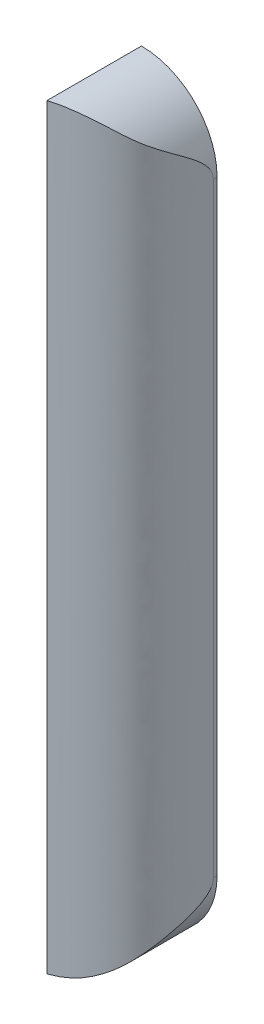
SolidWorks part; units mm, degrees
ref_plane "Front Plane" through (0, 0, 0) normal (0, 0, 1) x (1, 0, 0)
ref_plane "Top Plane" through (0, 0, 0) normal (0, 1, 0) x (1, 0, 0)
ref_plane "Right Plane" through (0, 0, 0) normal (1, 0, 0) x (0, 0, -1)
sketch "Sketch1" plane through (0, 0, 0) normal (0, 0, 1) x (1, 0, 0)
  line L1 (-4, 40) -> (4, 40)
  line L2 (-4, 40) -> (-4, -40)
  line L3 (-4, -40) -> (4, -40)
  line L4 (4, 40) -> (4, -40)
  point P4 (0, -40)
  point P6 (4, 0)
  dimension "D1" = 80
  dimension "D2" = 8
extrude "Extrude1" add sketch "Sketch1" along normal blind 0.4
sketch "Sketch2" plane through (0, -40, 0) normal (0, -1, 0) x (1, 0, 0)
  line L0 (-4, 0) -> (-4, 10)
  line L2 (4, 0.4) -> (4, 0)
  line L3 (4, 0) -> (-4, 0)
  spline S0 degree 3 poles (-4, 10) (-2.5404, 9.5034) (-0.7391, 8.8906) (2.8056, 5.9103) (3.4599, 2.8917) (4, 0.4) knots 0 0 0 0 0.42715 0.52715 1 1 1 1
  dimension "D1" = 10
extrude "Extrude2" add sketch "Sketch2" against normal up to surface (80 mm away) up to face at (0, 40, 0.2)
fillet "Fillet1" radius 8 2 edges at (4, 40, 0.2) (4, -40, 0.2)
shell "Shell1" thickness 1 removed face at (-4, 0, 5)
